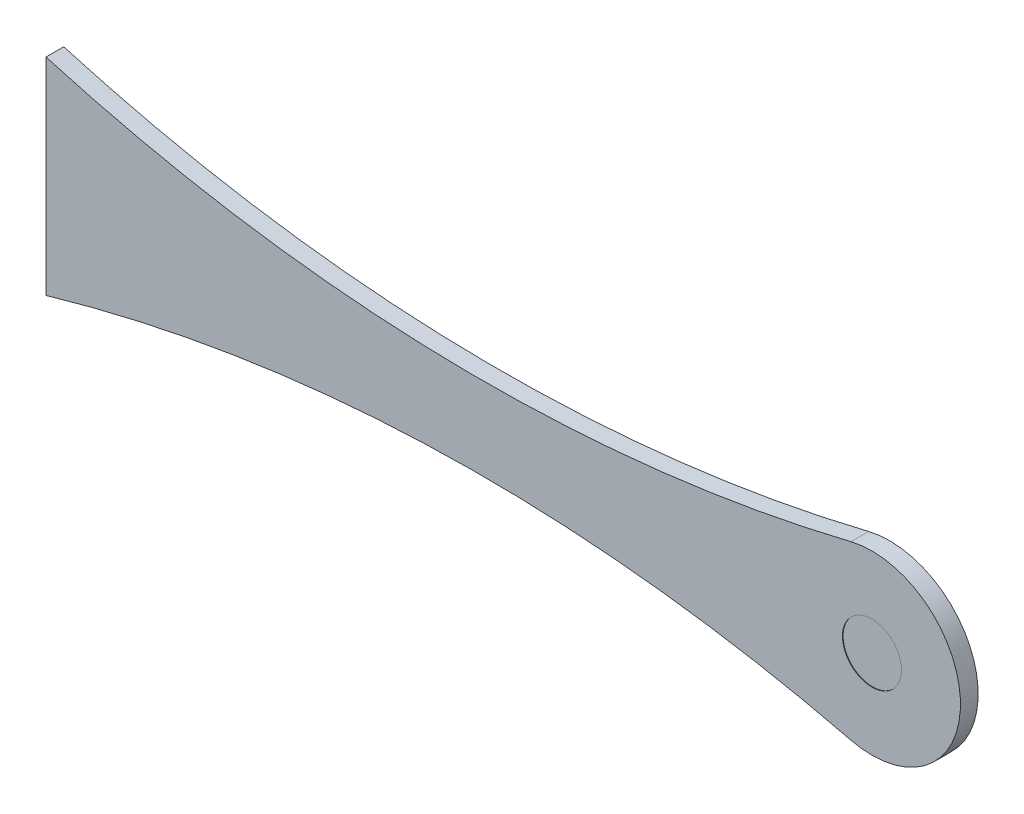
SolidWorks part; units mm, degrees
material "Custom Plastic"
ref_plane "Front Plane" through (0, 0, 0) normal (0, 0, 1) x (1, 0, 0)
ref_plane "Top Plane" through (0, 0, 0) normal (0, 1, 0) x (1, 0, 0)
ref_plane "Right Plane" through (0, 0, 0) normal (1, 0, 0) x (0, 0, -1)
sketch "Sketch1" plane through (0, 0, 0) normal (0, 1, 0) x (1, 0, 0)
  line L0 (0, 0) -> (-140, 0) construction
  line L1 (-140, 17.5) -> (-140, -17.5)
  line L2 (-66.3112, 7) -> (-140, 7) construction
  circle A0 centre (0, 0) radius 5
  arc A1 (-3.5674, 14.5696) -> (-3.5674, -14.5696) centre (0, 0) cw
  arc A2 (-3.5674, 14.5696) -> (-140, 17.5) centre (-66.3112, 270.8234) cw
  arc A3 (-3.5674, -14.5696) -> (-140, -17.5) centre (-66.3112, -270.8234) ccw
  point P13 (-140, 0)
  dimension "D1" = 5
  dimension "D2" = 15
  dimension "D3" = 7
  dimension "D4" = 140
  dimension "D5" = 35
  dimension "D6" = 155
extrude "Boss-Extrude1" add sketch "Sketch1" along normal mid plane 3
extrude "Boss-Extrude2" add sketch "Sketch1<3>" along normal offset from surface 0.1 and the other way offset from surface 0.1 contours A0 region at (0, 0, 0) up to face at (-67.2382, 1.5, 0) other way up to face at (-67.2382, -1.5, 0)
sketch "Sketch1<3>" plane through (0, 0, 0) normal (0, 1, 0) x (1, 0, 0) same geometry as "Sketch1"
move or copy body "Body-Move/Copy1" bodies to move or copy 102 copy no rotation origin (0, 0, 0) rotation axis (1, 0, 0) rotation angle 90
